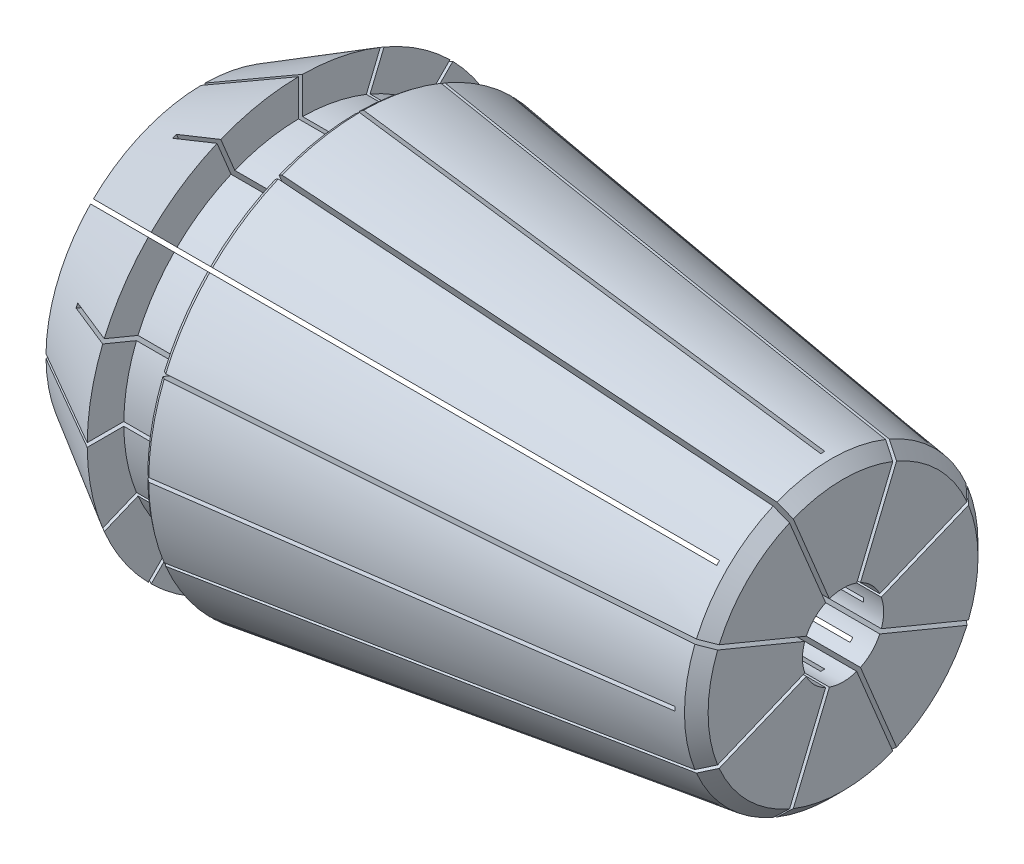
SolidWorks part; units mm, degrees
ref_plane "Front Plane" through (0, 0, 0) normal (0, 0, 1) x (1, 0, 0)
ref_plane "Top Plane" through (0, 0, 0) normal (0, 1, 0) x (1, 0, 0)
ref_plane "Right Plane" through (0, 0, 0) normal (1, 0, 0) x (0, 0, -1)
sketch "Sketch2" plane through (0, 0, 0) normal (1, 0, 0) x (0, 0, -1)
  circle A0 centre (0, 0) radius 10.5
  dimension "D1" = 21
extrude "Boss-Extrude1" add sketch "Sketch2" along normal blind 31.5
sketch "Sketch3" plane through (0, 0, 0) normal (0, 0, 1) x (1, 0, 0)
  line L0 (0, 0) -> (132.04, 0) construction
  line L1 (0, 7.7287) -> (4.8, 10.5)
  line L2 (0, 10.5) -> (0, -10.5) construction
  line L4 (4.8, 10.5) -> (4.8, 8.7)
  line L5 (4.8, 8.7) -> (7.6023, 8.7)
  line L6 (7.6023, 8.7) -> (7.6023, 10.5)
  line L7 (7.6023, 10.5) -> (31.5, 7.1414)
  line L8 (31.5, -10.5) -> (31.5, 10.5) construction
  line L9 (31.5, 7.1414) -> (31.5, 15.5)
  line L10 (31.5, 15.5) -> (0, 15.5)
  line L11 (0, 15.5) -> (0, 7.7287)
  line L13 (31.5, 10.5) -> (0, 10.5) construction
  line L15 (0, 0) -> (31.5, 0)
  line L16 (0, 0) -> (0, 2)
  line L17 (0, 2) -> (31.5, 2)
  line L18 (31.5, 0) -> (31.5, 2)
  point P9 (11.16, 10)
  dimension "D1" = 30
  dimension "D2" = 8
  dimension "D3" = 17.4
  dimension "D4" = 4.8
  dimension "D5" = 6.36
  dimension "D6" = 20
  dimension "D7" = 4
  dimension "D8" = 21
  dimension "D9" = 2.8023
  dimension "D10" = 5
revolve "Cut-Revolve1" cut sketch "Sketch3" angle 360 about L0
sketch "Sketch4" plane through (0, 0, 0) normal (-1, 0, 0) x (0, 0, 1)
  line L0 (21.8496, 21.991) -> (21.991, 21.8496)
  line L1 (-0.1, 31) -> (0.1, 31)
  line L2 (-0.1, 31) -> (-0.1, -31)
  line L3 (-0.1, -31) -> (0.1, -31)
  line L4 (0.1, 31) -> (0.1, -31)
  line L5 (-0.1, 31) -> (0.1, -31) construction
  line L6 (-0.1, -31) -> (0.1, 31) construction
  line L7 (21.8496, 21.991) -> (-21.991, -21.8496)
  line L8 (-21.991, -21.8496) -> (-21.8496, -21.991)
  line L9 (21.991, 21.8496) -> (-21.8496, -21.991)
  line L10 (21.8496, 21.991) -> (-21.8496, -21.991) construction
  line L11 (-21.991, -21.8496) -> (21.991, 21.8496) construction
  line L12 (31, 0.1) -> (31, -0.1)
  line L13 (31, 0.1) -> (-31, 0.1)
  line L14 (-31, 0.1) -> (-31, -0.1)
  line L15 (31, -0.1) -> (-31, -0.1)
  line L16 (31, 0.1) -> (-31, -0.1) construction
  line L17 (-31, 0.1) -> (31, -0.1) construction
  line L18 (21.991, -21.8496) -> (21.8496, -21.991)
  line L19 (21.991, -21.8496) -> (-21.8496, 21.991)
  line L20 (-21.8496, 21.991) -> (-21.991, 21.8496)
  line L21 (21.8496, -21.991) -> (-21.991, 21.8496)
  line L22 (21.991, -21.8496) -> (-21.991, 21.8496) construction
  line L23 (-21.8496, 21.991) -> (21.8496, -21.991) construction
  line L24 (0.1, -31) -> (-0.1, -31)
  line L25 (0.1, -31) -> (0.1, 31)
  line L26 (0.1, 31) -> (-0.1, 31)
  line L27 (-0.1, -31) -> (-0.1, 31)
  line L28 (0.1, -31) -> (-0.1, 31) construction
  line L29 (0.1, 31) -> (-0.1, -31) construction
  line L30 (-21.8496, -21.991) -> (-21.991, -21.8496)
  line L31 (-21.8496, -21.991) -> (21.991, 21.8496)
  line L32 (21.991, 21.8496) -> (21.8496, 21.991)
  line L33 (-21.991, -21.8496) -> (21.8496, 21.991)
  line L34 (-21.8496, -21.991) -> (21.8496, 21.991) construction
  line L35 (21.991, 21.8496) -> (-21.991, -21.8496) construction
  line L36 (-31, -0.1) -> (-31, 0.1)
  line L37 (-31, -0.1) -> (31, -0.1)
  line L38 (31, -0.1) -> (31, 0.1)
  line L39 (-31, 0.1) -> (31, 0.1)
  line L40 (-31, -0.1) -> (31, 0.1) construction
  line L41 (31, -0.1) -> (-31, 0.1) construction
  line L42 (-21.991, 21.8496) -> (-21.8496, 21.991)
  line L43 (-21.991, 21.8496) -> (21.8496, -21.991)
  line L44 (21.8496, -21.991) -> (21.991, -21.8496)
  line L45 (-21.8496, 21.991) -> (21.991, -21.8496)
  line L46 (-21.991, 21.8496) -> (21.991, -21.8496) construction
  line L47 (21.8496, -21.991) -> (-21.8496, 21.991) construction
  point P0 (0, 0)
  point P37 (0, 0)
  dimension "D3" = 31
  dimension "D1" = 0.2
  dimension "D2" = 8
extrude "Cut-Extrude1" cut sketch "Sketch4" against normal offset from surface (30.5 mm away) 1 contours L19 L20 L21 L18 | L13 L14 L15 L12 | L7 L8 L9 L0 | L4 L3 L2 L1 up to face at (31.5, 0, 2)
sketch "Sketch5" plane through (31.5, 0, 0) normal (1, 0, 0) x (0, 0, -1)
  line L0 (0, 0) -> (0, -5.7107) construction
  line L1 (-11.9556, -28.602) -> (-11.7708, -28.6785)
  line L2 (-11.9556, -28.602) -> (11.7708, 28.6785)
  line L3 (11.7708, 28.6785) -> (11.9556, 28.602)
  line L4 (-11.7708, -28.6785) -> (11.9556, 28.602)
  line L5 (-11.9556, -28.602) -> (11.9556, 28.602) construction
  line L6 (11.7708, 28.6785) -> (-11.7708, -28.6785) construction
  line L7 (28.602, 11.9556) -> (28.6785, 11.7708)
  line L8 (-28.602, -11.9556) -> (28.6785, 11.7708)
  line L9 (-28.6785, -11.7708) -> (28.602, 11.9556)
  line L10 (-28.6785, -11.7708) -> (-28.602, -11.9556)
  line L11 (28.6785, -11.7708) -> (28.602, -11.9556)
  line L12 (-28.6785, 11.7708) -> (28.602, -11.9556)
  line L13 (-28.602, 11.9556) -> (28.6785, -11.7708)
  line L14 (-28.602, 11.9556) -> (-28.6785, 11.7708)
  line L15 (11.9556, -28.602) -> (11.7708, -28.6785)
  line L16 (-11.9556, 28.602) -> (11.7708, -28.6785)
  line L17 (-11.7708, 28.6785) -> (11.9556, -28.602)
  line L18 (-11.7708, 28.6785) -> (-11.9556, 28.602)
  line L19 (-11.7708, -28.6785) -> (-11.9556, -28.602)
  line L20 (11.7708, 28.6785) -> (-11.9556, -28.602)
  line L21 (11.9556, 28.602) -> (-11.7708, -28.6785)
  line L22 (11.9556, 28.602) -> (11.7708, 28.6785)
  line L23 (-28.602, -11.9556) -> (-28.6785, -11.7708)
  line L24 (28.602, 11.9556) -> (-28.6785, -11.7708)
  line L25 (28.6785, 11.7708) -> (-28.602, -11.9556)
  line L26 (28.6785, 11.7708) -> (28.602, 11.9556)
  line L27 (-28.6785, 11.7708) -> (-28.602, 11.9556)
  line L28 (28.6785, -11.7708) -> (-28.602, 11.9556)
  line L29 (28.602, -11.9556) -> (-28.6785, 11.7708)
  line L30 (28.602, -11.9556) -> (28.6785, -11.7708)
  line L31 (-11.9556, 28.602) -> (-11.7708, 28.6785)
  line L32 (11.9556, -28.602) -> (-11.7708, 28.6785)
  line L33 (11.7708, -28.6785) -> (-11.9556, 28.602)
  line L34 (11.7708, -28.6785) -> (11.9556, -28.602)
  point P0 (0, 0)
  point P40 (0, 0)
  dimension "D1" = 0.2
  dimension "D2" = 22.5
  dimension "D3" = 8
extrude "Cut-Extrude2" cut sketch "Sketch5" against normal offset from surface (29.5 mm away) 2 contours L8 L7 L9 L10 | L12 L11 L13 L14 | L16 L15 L17 L18 | L4 L3 L2 L1 up to face at (0, 4.34, 1.7977)
chamfer "Фаска1" distance 0.5 angle 45 8 edges at (0, -1.8478, -0.7654) (0, -1.8478, 0.7654) (0, -0.7654, 1.8478) (0, 0.7654, 1.8478) (0, 1.8478, 0.7654) (0, 1.8478, -0.7654) (0, 0.7654, -1.8478) (0, -0.7654, -1.8478)
chamfer "Фаска2" distance 0.2 angle 45 16 edges at (7.6023, 2.0484, 10.2982) (7.6023, 5.8335, 8.7304) (7.6023, 8.7304, 5.8335) (7.6023, -2.0484, 10.2982) (7.6023, -5.8335, 8.7304) (7.6023, -8.7304, 5.8335) (7.6023, -10.2982, 2.0484) (7.6023, -10.2982, -2.0484) (7.6023, -8.7304, -5.8335) (7.6023, -5.8335, -8.7304) (7.6023, -2.0484, -10.2982) (7.6023, 2.0484, -10.2982) (7.6023, 5.8335, -8.7304) (7.6023, 8.7304, -5.8335) (7.6023, 10.2982, -2.0484) (7.6023, 10.2982, 2.0484)
chamfer "Фаска3" distance 0.5 angle 45 8 edges at (31.5, -7.1414, 0) (31.5, -5.0497, -5.0497) (31.5, 0, -7.1414) (31.5, 5.0497, -5.0497) (31.5, 7.1414, 0) (31.5, 5.0497, 5.0497) (31.5, 0, 7.1414) (31.5, -5.0497, 5.0497) first distance on face at (31.5, -4.4151, 0) first distance on face at (31.5, -3.122, -3.122) first distance on face at (31.5, 0, -4.4151) first distance on face at (31.5, 3.122, -3.122) first distance on face at (31.5, 4.4151, 0) first distance on face at (31.5, 3.122, 3.122) first distance on face at (31.5, 0, 4.4151) first distance on face at (31.5, -3.122, 3.122)
equation "\"L\"= 13.5"
